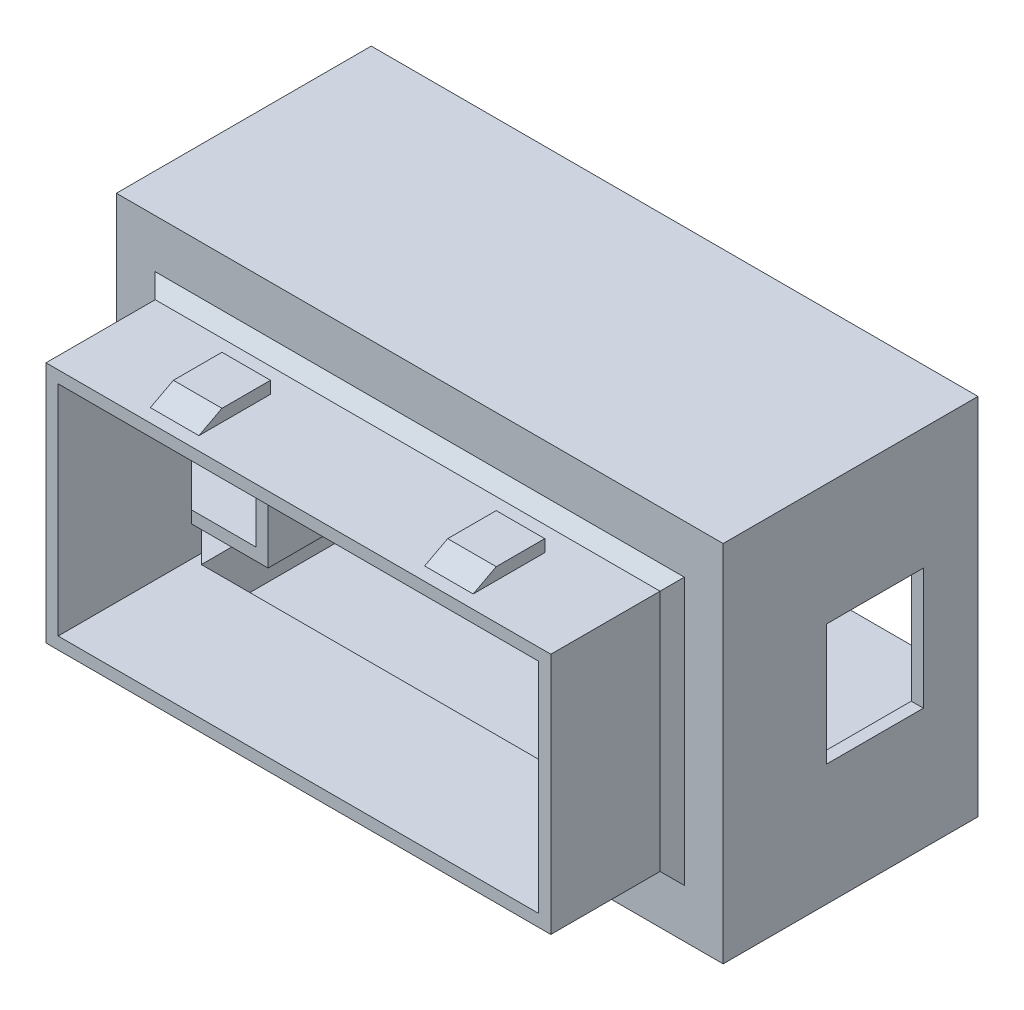
SolidWorks part; units mm, degrees
ref_plane "Front Plane" through (0, 0, 0) normal (0, 0, 1) x (1, 0, 0)
ref_plane "Top Plane" through (0, 0, 0) normal (0, 1, 0) x (1, 0, 0)
ref_plane "Right Plane" through (0, 0, 0) normal (1, 0, 0) x (0, 0, -1)
sketch "Sketch1" plane through (0, 0, 0) normal (0, 0, 1) x (1, 0, 0)
  line L0 (19.8, 9) -> (19.8, -9)
  line L1 (-20.8, 10) -> (20.8, 10)
  line L2 (-20.8, 10) -> (-20.8, -10)
  line L3 (-20.8, -10) -> (20.8, -10)
  line L4 (20.8, 10) -> (20.8, -10)
  line L5 (-20.8, 10) -> (20.8, -10) construction
  line L6 (-20.8, -10) -> (20.8, 10) construction
  line L7 (-19.8, -9) -> (19.8, -9)
  line L8 (-19.8, 9) -> (-19.8, -9)
  line L9 (-19.8, 9) -> (19.8, 9)
  point P0 (0, 0)
  dimension "D1" = 1
extrude "Boss-Extrude2" add sketch "Sketch1" along normal blind 10
sketch "Sketch2" plane through (0, -10, 0) normal (0, -1, 0) x (1, 0, 0)
  line L0 (0, 10) -> (0, 0)
  line L1 (-20.8, 10) -> (20.8, 10) construction
  line L3 (-9.3, 10) -> (9.3, 10)
  line L4 (-9.3, 10) -> (-9.3, 0)
  line L5 (-9.3, 0) -> (9.3, 0)
  line L6 (9.3, 10) -> (9.3, 0)
  line L7 (-9.3, 10) -> (9.3, 0) construction
  line L8 (-9.3, 0) -> (9.3, 10) construction
  line L9 (9.3, 10) -> (13.3, 10)
  line L10 (9.3, 10) -> (9.3, 0)
  line L11 (9.3, 0) -> (13.3, 0)
  line L12 (13.3, 10) -> (13.3, 0)
  line L13 (-9.3, 10) -> (-13.3, 10)
  line L14 (-9.3, 10) -> (-9.3, 0)
  line L15 (-9.3, 0) -> (-13.3, 0)
  line L16 (-13.3, 10) -> (-13.3, 0)
  point P5 (0, 5)
  line M1 (-20.8, 0) -> (20.8, 0)
  line M3 (20.8, 10) -> (-20.8, 10)
extrude "Boss-Extrude3" add sketch "Sketch2" along normal blind 1 contours L16 L4 M3 M1 | L12 L6 M3 M1
sketch "Sketch3" plane through (-13.3, 0, 0) normal (-1, 0, 0) x (0, 0, 1)
  line L0 (7, -11) -> (8.9001, -10)
  line L1 (10, -11) -> (7, -11)
  line L2 (10, -11) -> (10, -10)
  line L3 (10, -10) -> (7, -10)
  line L4 (7, -11) -> (7, -10)
  line L5 (0, -11) -> (0, -10) construction
  line L6 (7, -10) -> (3, -10)
  line L7 (7, -10) -> (7, -11)
  line L8 (7, -11) -> (3, -11)
  line L9 (3, -10) -> (3, -11)
  line L10 (3, -10) -> (0, -10)
  line L11 (3, -10) -> (3, -11)
  line L12 (3, -11) -> (0, -11)
  line L13 (0, -10) -> (0, -11)
  line L14 (10, -11) -> (0, -11) construction
  line M1 (10, -10) -> (0, -10)
  line M2 (0, -10) -> (0, -11)
  line M3 (0, -11) -> (10, -11)
  line M4 (10, -11) -> (10, -10)
extrude "Cut-Extrude1" cut sketch "Sketch3" against normal blind 27 contours L0 M3 M4 M1 | L9 M1 M2 M3
sketch "Sketch4" plane through (0, 10, 0) normal (0, 1, 0) x (1, 0, 0)
  line L0 (0, -10) -> (0, 0)
  line L1 (20.8, -10) -> (-20.8, -10) construction
  line L2 (20.8, 0) -> (-20.8, 0) construction
  line L4 (9.3, -10) -> (-9.3, -10)
  line L5 (9.3, -10) -> (9.3, 0)
  line L6 (9.3, 0) -> (-9.3, 0)
  line L7 (-9.3, -10) -> (-9.3, 0)
  line L8 (9.3, -10) -> (-9.3, 0) construction
  line L9 (9.3, 0) -> (-9.3, -10) construction
  line L10 (-9.3, -10) -> (-13.3, -10)
  line L11 (-9.3, -10) -> (-9.3, 0)
  line L12 (-9.3, 0) -> (-13.3, 0)
  line L13 (-13.3, -10) -> (-13.3, 0)
  line L14 (9.3, -10) -> (13.3, -10)
  line L15 (9.3, -10) -> (9.3, 0)
  line L16 (9.3, 0) -> (13.3, 0)
  line L17 (13.3, -10) -> (13.3, 0)
  point P6 (0, -5)
  line M1 (20.8, 0) -> (-20.8, 0)
  line M3 (-20.8, -10) -> (20.8, -10)
extrude "Boss-Extrude4" add sketch "Sketch4" along normal blind 1 contours L17 L5 M3 M1 | L13 L7 M3 M1
sketch "Sketch5" plane through (13.3, 0, 0) normal (1, 0, 0) x (0, 0, -1)
  line L1 (-10, 11) -> (0, 11) construction
  line L2 (-10, 10) -> (0, 10) construction
  line L3 (-10, 11) -> (-7, 11)
  line L4 (-10, 11) -> (-10, 10)
  line L5 (-10, 10) -> (-7, 10)
  line L6 (-7, 11) -> (-7, 10)
  line L7 (-10, 10) -> (0, 10) construction
  line L8 (-7, 11) -> (-3, 11)
  line L9 (-7, 11) -> (-7, 10)
  line L10 (-7, 10) -> (-3, 10)
  line L11 (-3, 11) -> (-3, 10)
  line L12 (-7, 11) -> (-8.9001, 10)
  line M1 (-10, 10) -> (0, 10)
  line M2 (0, 10) -> (0, 11)
  line M3 (0, 11) -> (-10, 11)
  line M4 (-10, 11) -> (-10, 10)
extrude "Cut-Extrude2" cut sketch "Sketch5" against normal blind 27 contours L12 M3 M4 M1 | L11 M3 M1 M2
sketch "Sketch6" plane through (0, 0, 0) normal (0, 0, -1) x (-1, 0, 0)
  line L0 (19.8, -9) -> (-19.8, -9) construction
  line L1 (-20.8, 10) -> (20.8, 10)
  line L2 (-20.8, 10) -> (-20.8, -10)
  line L3 (-20.8, -10) -> (20.8, -10)
  line L4 (20.8, 10) -> (20.8, -10)
  line L5 (-20.8, 10) -> (20.8, -10) construction
  line L6 (-20.8, -10) -> (20.8, 10) construction
  line L7 (-19.8, 9) -> (19.8, 9)
  line L8 (-19.8, 9) -> (-19.8, -9)
  line L9 (-19.8, -9) -> (19.8, -9)
  line L10 (19.8, 9) -> (19.8, -9)
  line L11 (-19.8, 9) -> (19.8, -9) construction
  line L12 (-19.8, -9) -> (19.8, 9) construction
  line L14 (-25, 15) -> (25, 15)
  line L15 (-25, 15) -> (-25, -15)
  line L16 (-25, -15) -> (25, -15)
  line L17 (25, 15) -> (25, -15)
  line L18 (-25, 15) -> (25, -15) construction
  line L19 (-25, -15) -> (25, 15) construction
  point P0 (0, 0)
  point P7 (0, 0)
  point P14 (0, 0)
  line M1 (20.8, -10) -> (20.8, 10)
  line M2 (20.8, 10) -> (-20.8, 10)
  line M3 (-20.8, 10) -> (-20.8, -10)
  line M4 (-20.8, -10) -> (20.8, -10)
  line M5 (-19.8, 9) -> (19.8, 9)
  line M6 (19.8, 9) -> (19.8, -9)
  line M7 (19.8, -9) -> (-19.8, -9)
  line M8 (-19.8, -9) -> (-19.8, 9)
extrude "Boss-Extrude6" add sketch "Sketch6" along normal blind 1 contours M4 M1 M2 M3 M8 M5 M6 M7 | L17 L14 L15 L16 M1 M4 M3 M2
chamfer "Chamfer1" distance 1 angle 45 4 edges at (-20.8, 0, 0) (20.8, 0, 0)
sketch "Sketch7" plane through (0, 0, -1) normal (0, 0, -1) x (-1, 0, 0)
  line L0 (-25, 15) -> (25, 15)
  line L1 (-24, 14) -> (24, 14)
  line L2 (-24, 14) -> (-24, -14)
  line L3 (-24, -14) -> (24, -14)
  line L4 (24, 14) -> (24, -14)
  line L5 (-24, 14) -> (24, -14) construction
  line L6 (-24, -14) -> (24, 14) construction
  line L7 (25, 15) -> (25, -15)
  line L8 (-25, -15) -> (25, -15)
  line L9 (-25, 15) -> (-25, -15)
  point P0 (0, 0)
  dimension "D1" = 1
extrude "Boss-Extrude7" add sketch "Sketch7" along normal blind 20
sketch "Sketch8" plane through (0, 0, -1) normal (0, 0, -1) x (-1, 0, 0)
  line L0 (-19.8, 0) -> (-24, 0)
  line L1 (-19.8, -9) -> (-19.8, 9) construction
  line L2 (-24, 14) -> (-24, -14) construction
  line L5 (-24, 6) -> (-14, 6)
  line L6 (-24, 5) -> (-15, 5)
  line L7 (-24, 5) -> (-24, -5)
  line L8 (-24, -5) -> (-15, -5)
  line L9 (-15, 5) -> (-15, -5)
  line L10 (-14, 6) -> (-14, -6)
  line L11 (-24, -6) -> (-14, -6)
  line M3 (-24, 14) -> (-24, -14)
  line M5 (-19.8, -9) -> (-19.8, 9)
  dimension "D1" = 1
extrude "Boss-Extrude8" add sketch "Sketch8" along normal blind 20 contours L11 L10 L5 L6 L9 L8 M5 | L6 L5 M3 M5 | L11 L8 M3 M5
sketch "Sketch9" plane through (0, 0, -1) normal (0, 0, -1) x (-1, 0, 0)
  line L0 (19.8, 0) -> (24, 0)
  line L1 (19.8, 9) -> (19.8, -9) construction
  line L2 (24, -14) -> (24, 14) construction
  line L3 (24, 0) -> (24, -5)
  line L4 (24, 0) -> (24, 5)
  line L5 (24, 6) -> (14, 6)
  line L6 (24, 5) -> (15, 5)
  line L7 (24, 5) -> (24, -5)
  line L8 (24, -5) -> (15, -5)
  line L9 (15, 5) -> (15, -5)
  line L10 (14, 6) -> (14, -6)
  line L11 (24, -6) -> (14, -6)
  line M5 (24, -14) -> (24, 14)
  line M11 (19.8, 9) -> (19.8, -9)
  dimension "D1" = 1
extrude "Boss-Extrude9" add sketch "Sketch9" along normal blind 20 contours L11 L8 L9 L6 L5 L10 M11 | L6 L5 M5 M11 | L11 L8 M5 M11
sketch "Sketch10" plane through (0, 0, -1) normal (0, 0, -1) x (-1, 0, 0)
  line L0 (-24, -6) -> (-24, -14) construction
  line L1 (-24, 14) -> (-20, 14)
  line L2 (-24, 14) -> (-24, 10)
  line L3 (-24, 10) -> (-20, 10)
  line L4 (-20, 14) -> (-20, 10)
  line L5 (24, 14) -> (20, 14)
  line L6 (24, 14) -> (24, 10)
  line L7 (24, 10) -> (20, 10)
  line L8 (20, 14) -> (20, 10)
  line L9 (24, -14) -> (20, -14)
  line L10 (24, -14) -> (24, -10)
  line L11 (24, -10) -> (20, -10)
  line L12 (20, -14) -> (20, -10)
  line L13 (-24, -14) -> (-20, -14)
  line L14 (-24, -14) -> (-24, -10)
  line L15 (-24, -10) -> (-20, -10)
  line L16 (-20, -14) -> (-20, -10)
extrude "Boss-Extrude10" add sketch "Sketch10" along normal blind 20
sketch "Sketch11" plane through (-25, 0, 0) normal (-1, 0, 0) x (0, 0, 1)
  line L0 (-10.5, 15) -> (-10.5, -15)
  line L1 (-21, 15) -> (0, 15) construction
  line L2 (-21, -15) -> (0, -15) construction
  line L3 (-16.5, 0) -> (-16.5, 5)
  line L4 (-21, -15) -> (-21, 15) construction
  line L5 (-21, 0) -> (-16.5, 0)
  line L6 (-16.5, 0) -> (-16.5, -5)
  line L8 (-16.5, 5) -> (-8.5, 5)
  line L9 (-16.5, 5) -> (-16.5, -5)
  line L10 (-16.5, -5) -> (-8.5, -5)
  line L11 (-8.5, 5) -> (-8.5, -5)
extrude "Cut-Extrude3" cut sketch "Sketch11" against normal blind 1 contours L6 L10 L0 L8 L3 | L11 L8 L0 L10
sketch "Sketch12" plane through (25, 0, 0) normal (1, 0, 0) x (0, 0, -1)
  line L0 (10.5, 15) -> (10.5, -15)
  line L1 (21, 15) -> (0, 15) construction
  line L2 (21, -15) -> (0, -15) construction
  line L3 (16.5, 0) -> (16.5, 5)
  line L4 (21, 15) -> (21, -15) construction
  line L5 (21, 0) -> (16.5, 0)
  line L6 (16.5, 0) -> (16.5, -5)
  line L8 (16.5, -5) -> (8.5, -5)
  line L9 (16.5, -5) -> (16.5, 5)
  line L10 (16.5, 5) -> (8.5, 5)
  line L11 (8.5, -5) -> (8.5, 5)
extrude "Cut-Extrude4" cut sketch "Sketch12" against normal blind 1 contours L11 L8 L0 L10 | L3 L10 L0 L8 L6
sketch "Sketch13" plane through (0, 0, -21) normal (0, 0, -1) x (-1, 0, 0)
  line L0 (-20, 10) -> (-25, 15)
  line L1 (20, 10) -> (25, 15)
  line L2 (-20, -10) -> (-25, -15)
  line L3 (-25, 15) -> (-25, -15) construction
  line L4 (-25, -15) -> (25, -15) construction
  line L5 (20, -10) -> (25, -15)
  circle A0 centre (-22.5, 12.5) radius 1.5
  circle A1 centre (22.5, 12.5) radius 1.5
  circle A2 centre (22.5, -12.5) radius 1.5
  circle A3 centre (-22.5, -12.5) radius 1.5
extrude "Cut-Extrude5" cut sketch "Sketch13" against normal blind 10 contours A0 | A1 | A2 | A3
chamfer "Chamfer2" distance 5 angle 45 2 edges at (0, -14, -1) (0, 14, -1)
chamfer "Chamfer3" distance 5 angle 45 4 edges at (24, -7.5, -1) (-24, -7.5, -1) (-24, 7.5, -1) (24, 7.5, -1)
chamfer "Chamfer4" distance 4 angle 45 2 edges at (24, 0, -1) (-24, 0, -1)
sketch "Sketch17" plane through (14, 0, 0) normal (-1, 0, 0) x (0, 0, 1)
  line L1 (-21, 6) -> (-1, -6)
  line L2 (-21, -6) -> (-1, 6)
  line L4 (-21, 7) -> (-1, 7)
  line L5 (-21, 7) -> (-21, -7)
  line L6 (-21, -7) -> (-1, -7)
  line L7 (-1, 7) -> (-1, -7)
  line L8 (-21, 7) -> (-1, -7) construction
  line L9 (-21, -7) -> (-1, 7) construction
  point P4 (-11, 0)
extrude "Cut-Extrude8" cut sketch "Sketch17" against normal blind 10 contours L5 L6 L7 L4
sketch "Sketch18" plane through (0, 0, -1) normal (0, 0, -1) x (-1, 0, 0)
  line L0 (-24, 0) -> (-24, 5.5)
  line L1 (-24, 0) -> (-24, -5.5)
  line L2 (-24, -6.5) -> (-13.5, -6.5)
  line L3 (-24, 5.5) -> (-14.5, 5.5)
  line L4 (-24, 5.5) -> (-24, -5.5)
  line L5 (-24, -5.5) -> (-14.5, -5.5)
  line L6 (-14.5, 5.5) -> (-14.5, -5.5)
  line L7 (-13.5, 6.5) -> (-13.5, -6.5)
  line L8 (-24, 6.5) -> (-13.5, 6.5)
  line M2 (-19.8, -7) -> (-19.8, 7)
  line M4 (-24, 7) -> (-24, -7)
  dimension "D1" = 1
extrude "Boss-Extrude11" add sketch "Sketch18" along normal blind 20 contours L8 L3 L6 L5 L2 L7 M2 | L8 L3 M4 M2 | L5 L2 M4 M2
chamfer "Chamfer5" distance 5 angle 45 2 edges at (19.8, 6.75, -1) (24, 6.75, -1)
chamfer "Chamfer6" distance 5 angle 45 2 edges at (19.8, -6.75, -1) (24, -6.75, -1)
chamfer "Chamfer7" distance 4 angle 45 1 edges at (24, 0, -1)
sketch "Sketch19" plane through (-14, 0, 0) normal (1, 0, 0) x (0, 0, -1)
  line L0 (1, 6) -> (21, -6)
  line L2 (1, 7) -> (21, 7)
  line L3 (1, 7) -> (1, -7)
  line L4 (1, -7) -> (21, -7)
  line L5 (21, 7) -> (21, -7)
  line L6 (1, 7) -> (21, -7) construction
  line L7 (1, -7) -> (21, 7) construction
  point P4 (11, 0)
extrude "Cut-Extrude9" cut sketch "Sketch19" against normal blind 10 contours L3 L4 L5 L2
sketch "Sketch20" plane through (0, 0, -1) normal (0, 0, -1) x (-1, 0, 0)
  line L0 (19.8, 0) -> (24, 0)
  line L1 (19.8, 7) -> (19.8, -7) construction
  line L2 (24, 7) -> (24, -7) construction
  line L3 (24, 0) -> (24, 5.5)
  line L4 (24, 0) -> (24, -5.5)
  line L5 (24, 6.5) -> (13.5, 6.5)
  line L6 (24, 5.5) -> (14.5, 5.5)
  line L7 (24, 5.5) -> (24, -5.5)
  line L8 (24, -5.5) -> (14.5, -5.5)
  line L9 (14.5, 5.5) -> (14.5, -5.5)
  line L10 (13.5, 6.5) -> (13.5, -6.5)
  line L11 (24, -6.5) -> (13.5, -6.5)
  line M1 (19.8, 7) -> (19.8, -7)
  line M3 (24, -7) -> (24, 7)
  dimension "D1" = 1
extrude "Boss-Extrude12" add sketch "Sketch20" along normal blind 20 contours L11 L8 L9 L6 L5 L10 M1 | L6 L5 M3 M1 | L11 L8 M3 M1
chamfer "Chamfer8" distance 4 angle 45 1 edges at (-24, 0, -1)
chamfer "Chamfer9" distance 5 angle 45 4 edges at (-19.8, -6.75, -1) (-24, -6.75, -1) (-19.8, 6.75, -1) (-24, 6.75, -1)
